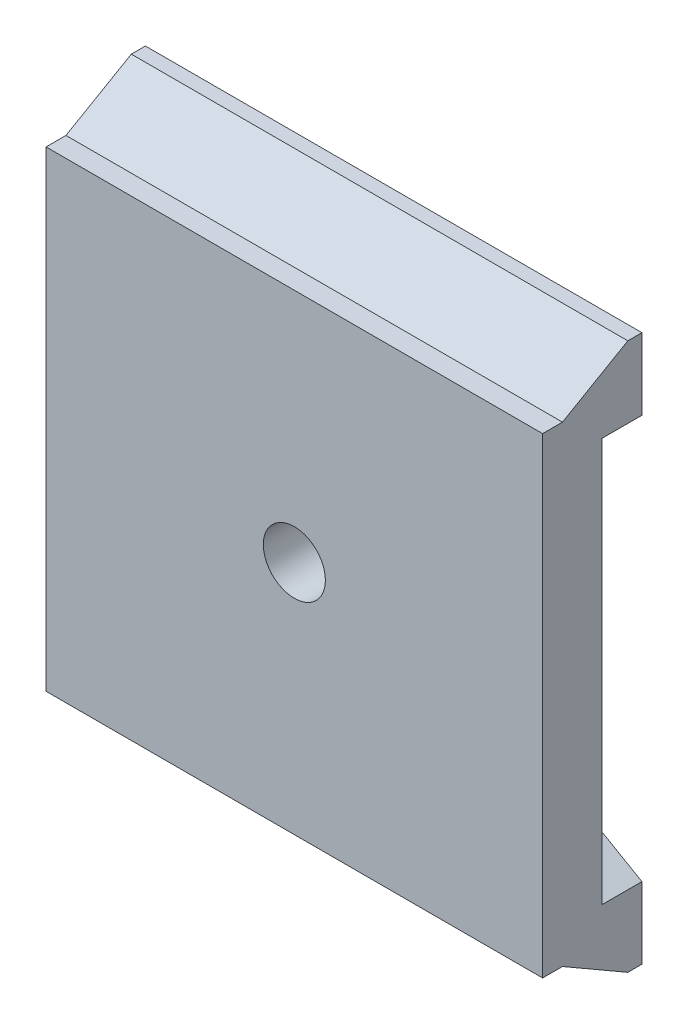
SolidWorks part; units mm, degrees
ref_plane "Front Plane" through (0, 0, 0) normal (0, 0, 1) x (1, 0, 0)
ref_plane "Top Plane" through (0, 0, 0) normal (0, 1, 0) x (1, 0, 0)
ref_plane "Right Plane" through (0, 0, 0) normal (1, 0, 0) x (0, 0, -1)
sketch "Sketch1" plane through (0, 0, 0) normal (0, 0, 1) x (1, 0, 0)
  line L1 (-25.4, 27.9781) -> (25.4, 27.9781)
  line L2 (-25.4, 27.9781) -> (-25.4, -27.9781)
  line L3 (-25.4, -27.9781) -> (25.4, -27.9781)
  line L4 (25.4, 27.9781) -> (25.4, -27.9781)
  line L5 (-25.4, 27.9781) -> (25.4, -27.9781) construction
  line L6 (-25.4, -27.9781) -> (25.4, 27.9781) construction
  point P0 (0, 0)
  dimension "D1" = 50.8
  dimension "D2" = 55.9562
extrude "Boss-Extrude1" add sketch "Sketch1" along normal blind 10.16
sketch "Sketch2" plane through (0, 0, 10.16) normal (0, 0, 1) x (1, 0, 0)
  line L0 (25.4, -27.9781) -> (25.4, 27.9781) construction
  line L1 (-25.4, 27.9781) -> (25.4, 27.9781)
  line L2 (-25.4, 27.9781) -> (-25.4, 24.1173)
  line L3 (-25.4, 24.1173) -> (25.4, 24.1173)
  line L4 (25.4, 27.9781) -> (25.4, 24.1173)
  line L6 (-25.4, -27.9781) -> (25.4, -27.9781)
  line L7 (-25.4, -27.9781) -> (-25.4, -24.1173)
  line L8 (-25.4, -24.1173) -> (25.4, -24.1173)
  line L9 (25.4, -27.9781) -> (25.4, -24.1173)
  dimension "D1" = 3.8608
  dimension "D2" = 3.8608
extrude "Cut-Extrude1" cut sketch "Sketch2" against normal blind 2.032
sketch "Sketch3" plane through (-25.4, 0, 0) normal (-1, 0, 0) x (0, 0, 1)
  line L0 (8.128, 24.1173) -> (1.4409, 27.9781)
  line L1 (8.128, 27.9781) -> (0, 27.9781) construction
  line L2 (1.4409, 27.9781) -> (8.128, 27.9781)
  line L3 (8.128, 27.9781) -> (8.128, 24.1173)
  line L4 (8.128, -24.1173) -> (1.4409, -27.9781)
  line L5 (8.128, -27.9781) -> (0, -27.9781) construction
  line L6 (1.4409, -27.9781) -> (8.128, -27.9781)
  line L7 (8.128, -27.9781) -> (8.128, -24.1173)
  dimension "D1" = 30
  dimension "D2" = 30
extrude "Cut-Extrude2" cut sketch "Sketch3" against normal through all
sketch "Sketch4" plane through (0, 0, 10.16) normal (0, 0, 1) x (1, 0, 0)
  circle A0 centre (0, 0) radius 3.175
  dimension "D1" = 6.35
extrude "Cut-Extrude3" cut sketch "Sketch4" against normal through all
sketch "Sketch5" plane through (0, 0, 0) normal (0, 0, -1) x (-1, 0, 0)
  line L0 (25.4, 27.9781) -> (25.4, -27.9781) construction
  line L1 (-25.4, -16.9926) -> (25.4, -16.9926)
  line L2 (-25.4, -16.9926) -> (-25.4, 16.9926)
  line L3 (-25.4, 16.9926) -> (25.4, 16.9926)
  line L4 (25.4, -16.9926) -> (25.4, 16.9926)
  line L5 (-25.4, -16.9926) -> (25.4, 16.9926) construction
  line L6 (-25.4, 16.9926) -> (25.4, -16.9926) construction
  point P0 (0, 0)
  dimension "D1" = 33.9852
extrude "Cut-Extrude4" cut sketch "Sketch5" against normal blind 4.064
sketch "Sketch6" plane through (0, 0, 0) normal (0, 0, -1) x (-1, 0, 0)
  line L1 (12.7, 21.0058) -> (-12.7, 21.0058)
  line L2 (15.875, 17.8308) -> (15.875, -17.8308)
  line L3 (12.7, -21.0058) -> (-12.7, -21.0058)
  line L4 (-15.875, 17.8308) -> (-15.875, -17.8308)
  line L5 (15.875, 21.0058) -> (-15.875, -21.0058) construction
  line L6 (15.875, -21.0058) -> (-15.875, 21.0058) construction
  arc A0 (12.7, 21.0058) -> (15.875, 17.8308) centre (12.7, 17.8308) cw
  arc A1 (15.875, -17.8308) -> (12.7, -21.0058) centre (12.7, -17.8308) cw
  arc A2 (-12.7, -21.0058) -> (-15.875, -17.8308) centre (-12.7, -17.8308) cw
  arc A3 (-12.7, 21.0058) -> (-15.875, 17.8308) centre (-12.7, 17.8308) ccw
  point P1 (0, 0)
  dimension "D3" = 3.175
  dimension "D1" = 42.0116
  dimension "D2" = 31.75
extrude "Cut-Extrude5" cut sketch "Sketch6" against normal blind 4.064
sketch "Sketch7" plane through (0, 0, 0) normal (0, 0, -1) x (-1, 0, 0)
  line L0 (-19.05, 16.9926) -> (-25.4, 20.6588)
  line L1 (-15.875, 16.9926) -> (-25.4, 16.9926) construction
  line L2 (-25.4, 16.9926) -> (-25.4, 27.9781) construction
  line L3 (-25.4, 20.6588) -> (-25.4, 16.9926)
  line L4 (-25.4, 16.9926) -> (-19.05, 16.9926)
  line L5 (-19.05, -16.9926) -> (-25.4, -20.6588)
  line L6 (-25.4, -16.9926) -> (-15.875, -16.9926) construction
  line L7 (-25.4, -27.9781) -> (-25.4, -16.9926) construction
  line L8 (-25.4, -20.6588) -> (-25.4, -16.9926)
  line L9 (-25.4, -16.9926) -> (-19.05, -16.9926)
  line L10 (19.05, -16.9926) -> (25.4, -20.6588)
  line L11 (25.4, -16.9926) -> (25.4, -27.9781) construction
  line L12 (25.4, -20.6588) -> (25.4, -16.9926)
  line L13 (25.4, -16.9926) -> (19.05, -16.9926)
  line L14 (19.05, 16.9926) -> (25.4, 20.6588)
  line L15 (25.4, 16.9926) -> (15.875, 16.9926) construction
  line L16 (25.4, 27.9781) -> (25.4, 16.9926) construction
  line L17 (25.4, 20.6588) -> (25.4, 16.9926)
  line L18 (25.4, 16.9926) -> (19.05, 16.9926)
  dimension "D1" = 6.35
  dimension "D2" = 6.35
  dimension "D3" = 6.35
  dimension "D4" = 6.35
  dimension "D5" = 30
  dimension "D6" = 30
extrude "Cut-Extrude6" cut sketch "Sketch7" against normal blind 4.064
